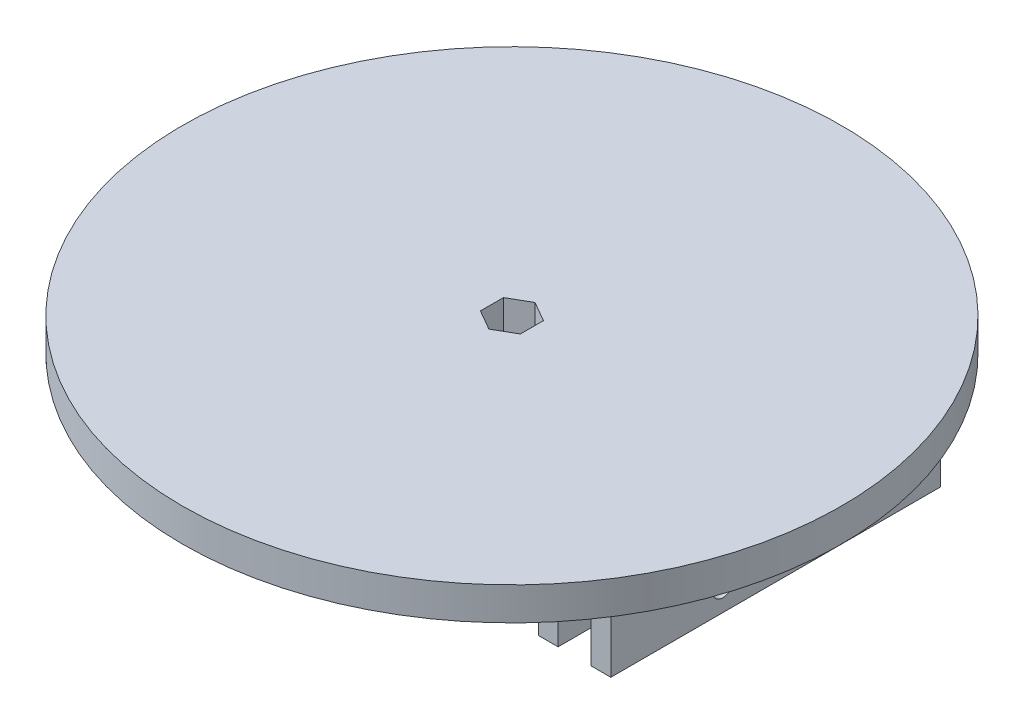
SolidWorks part; units mm, degrees
ref_plane "Front Plane" through (0, 0, 0) normal (0, 0, 1) x (1, 0, 0)
ref_plane "Top Plane" through (0, 0, 0) normal (0, 1, 0) x (1, 0, 0)
ref_plane "Right Plane" through (0, 0, 0) normal (1, 0, 0) x (0, 0, -1)
sketch "Sketch2" plane through (0, 0, 0) normal (0, 1, 0) x (1, 0, 0)
  circle A0 centre (0, 0) radius 9
extrude "Boss-Extrude1" add sketch "Sketch2" along normal blind 20
sketch "Sketch3" plane through (0, 20, 0) normal (0, 1, 0) x (1, 0, 0)
  line L0 (-3.0311, -1.75) -> (3.0311, 1.75) construction
  line L1 (0, -3.5) -> (0, 3.5) construction
  line L2 (3.0311, -1.75) -> (-3.0311, 1.75) construction
  line L15 (0, 3.5) -> (-3.0311, 1.75)
  line L16 (-3.0311, 1.75) -> (-3.0311, -1.75)
  line L17 (-3.0311, -1.75) -> (0, -3.5)
  line L18 (0, -3.5) -> (3.0311, -1.75)
  line L19 (3.0311, -1.75) -> (3.0311, 1.75)
  line L20 (3.0311, 1.75) -> (0, 3.5)
  circle A0 centre (0, 0) radius 3.5 construction
  point P4 (0, 0)
  point P5 (0, 0)
  point P6 (0, 0)
  point P9 (0, 0)
  point P10 (0, 0)
  point P11 (0, 0)
  point P14 (0, 0)
  point P15 (0, 0)
  point P17 (0, 0)
  point P20 (0, 0)
extrude "Cut-Extrude1" cut sketch "Sketch3" against normal blind 20
sketch "Sketch4" plane through (0, 20, 0) normal (0, 1, 0) x (1, 0, 0)
  circle A0 centre (0, 0) radius 50
  circle A1 centre (0, 0) radius 4.5
extrude "Boss-Extrude3" add sketch "Sketch4" against normal blind 5
ref_plane "Plane3" through (0, 0, 0) normal (0.5, 0, -0.866) x (-0.866, 0, -0.5)
sketch "Sketch11" plane through (0, 0, 0) normal (0.5, 0, -0.866) x (-0.866, 0, -0.5)
  line L2 (0, 0) -> (0, 5) construction
  circle A0 centre (0, 5) radius 1.55
extrude "Cut-Extrude2" cut sketch "Sketch11" against normal blind 9 and the other way blind 9
ref_plane "Plane4" through (0, 0, 0) normal (-0.5, 0, -0.866) x (-0.866, 0, 0.5)
sketch "Sketch15" plane through (0, 0, 0) normal (-0.5, 0, -0.866) x (-0.866, 0, 0.5)
  line L0 (0, 0) -> (0, 9) construction
  circle A0 centre (0, 9) radius 1.55
extrude "Cut-Extrude9" cut sketch "Sketch15" against normal blind 9 and the other way blind 9
sketch "Sketch16" plane through (0, 15, 0) normal (0, -1, 0) x (1, 0, 0)
  line L0 (0, 0) -> (32, 0) construction
  line L6 (0, 0) -> (-32, 0) construction
  line L12 (-32, -25) -> (-32, 25)
  line L13 (-32, 25) -> (-29, 25)
  line L14 (-29, 25) -> (-29, -25)
  line L15 (-29, -25) -> (-32, -25)
  line L16 (-32, 0) -> (-37, 0) construction
  line L17 (-37, -25) -> (-37, 25)
  line L18 (-37, 25) -> (-40, 25)
  line L19 (-40, 25) -> (-40, -25)
  line L20 (-40, -25) -> (-37, -25)
  line L21 (32, -25) -> (32, 25)
  line L22 (32, 25) -> (29, 25)
  line L23 (29, 25) -> (29, -25)
  line L24 (29, -25) -> (32, -25)
  line L25 (32, 0) -> (37, 0) construction
  line L26 (37, -25) -> (37, 25)
  line L27 (37, 25) -> (40, 25)
  line L28 (40, 25) -> (40, -25)
  line L29 (40, -25) -> (37, -25)
  point P7 (-32, 0)
  point P14 (-37, 0)
  point P19 (32, 0)
  point P25 (37, 0)
extrude "Boss-Extrude4" add sketch "Sketch16" along normal blind 10
sketch "Sketch17" plane through (-40, 0, 0) normal (-1, 0, 0) x (0, 0, 1)
  line L0 (-25, 5) -> (-25, 8.5) construction
  line L1 (-25, 5) -> (-25, 15) construction
  line L2 (-25, 8.5) -> (-8, 8.5) construction
  line L3 (-8, 8.5) -> (8, 8.5) construction
  line L4 (-16, 11.5) -> (16, 11.5) construction
  line L5 (-25, 15) -> (-25, 11.5) construction
  line L6 (-25, 11.5) -> (-16, 11.5) construction
  circle A0 centre (-16, 11.5) radius 1.55
  circle A1 centre (-8, 8.5) radius 1.55
  circle A3 centre (8, 8.5) radius 1.55
  circle A5 centre (16, 11.5) radius 1.55
extrude "Cut-Extrude10" cut sketch "Sketch17" against normal up to surface (11 mm away) up to face at (-29, 10, 0)
sketch "Sketch18" plane through (40, 0, 0) normal (1, 0, 0) x (0, 0, -1)
  line L0 (-25, 5) -> (-25, 8.5) construction
  line L1 (-25, 8.5) -> (-8, 8.5) construction
  line L2 (-8, 8.5) -> (8, 8.5) construction
  line L3 (8, 8.5) -> (-8, 8.5) construction
  line L4 (-25, 15) -> (-25, 11.5) construction
  line L5 (-25, 5) -> (-25, 15) construction
  line L6 (-25, 11.5) -> (-16, 11.5) construction
  line L7 (-16, 11.5) -> (16, 11.5) construction
  line L8 (16, 11.5) -> (-16, 11.5) construction
  circle A0 centre (-8, 8.5) radius 1.55
  circle A1 centre (8, 8.5) radius 1.55
  circle A2 centre (16, 11.5) radius 1.55
  circle A3 centre (-16, 11.5) radius 1.55
extrude "Cut-Extrude11" cut sketch "Sketch18" against normal up to surface (11 mm away) up to face at (29, 10, 0)
sketch "Sketch19" plane through (0, 0, 0) normal (-0.5, 0, -0.866) x (-0.866, 0, 0.5)
  circle A0 centre (0, 9) radius 3.5
extrude "Cut-Extrude14" cut sketch "Sketch19" against normal blind 3 from offset 9 contours A0
extrude "Cut-Extrude15" cut sketch "Sketch19<3>" along normal blind 3 from offset 9 offset against normal yes
sketch "Sketch19<3>" plane through (0, 0, 0) normal (-0.5, 0, -0.866) x (-0.866, 0, 0.5) same geometry as "Sketch19"
sketch "Sketch20" plane through (0, 0, 0) normal (0.5, 0, -0.866) x (-0.866, 0, -0.5)
  circle A0 centre (0, 5) radius 3.5
extrude "Cut-Extrude16" cut sketch "Sketch20" against normal blind 3 from offset 9
extrude "Cut-Extrude17" cut sketch "Sketch20<2>" along normal blind 3 from offset 9 offset against normal yes
sketch "Sketch20<2>" plane through (0, 0, 0) normal (0.5, 0, -0.866) x (-0.866, 0, -0.5) same geometry as "Sketch20"
